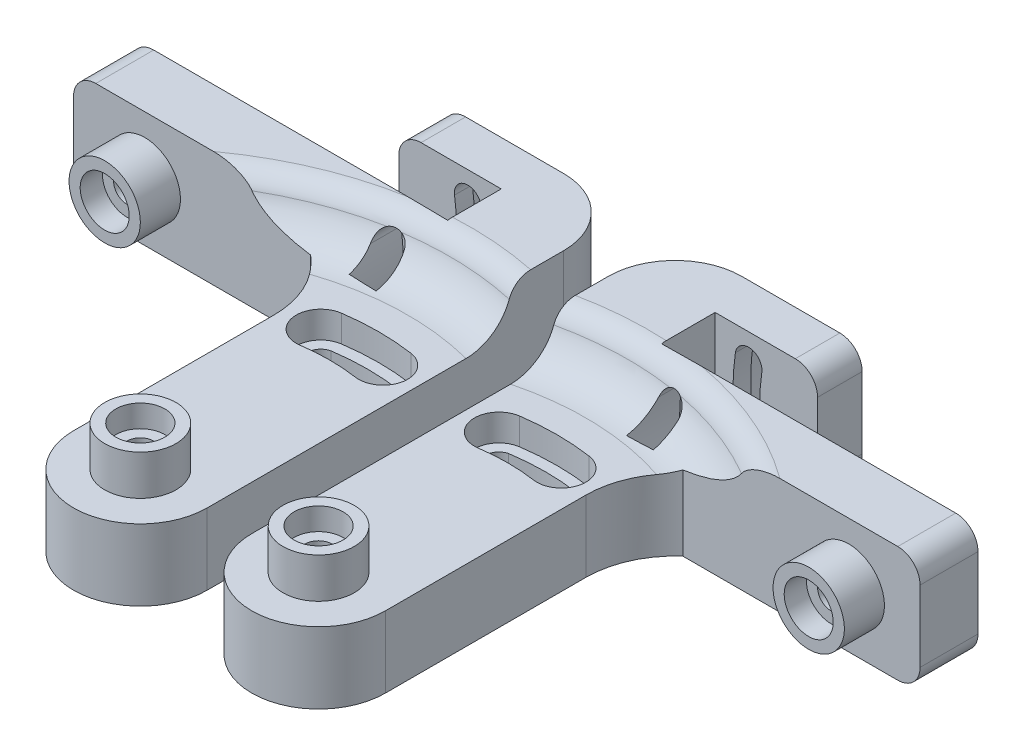
SolidWorks part; units mm, degrees
note: The reader was unsure of these and kept them because the rebuilt part matched: shared geometry of "Sketch6<8>".
ref_plane "Front Plane" through (0, 0, 0) normal (0, 0, 1) x (1, 0, 0)
ref_plane "Top Plane" through (0, 0, 0) normal (0, 1, 0) x (1, 0, 0)
ref_plane "Right Plane" through (0, 0, 0) normal (1, 0, 0) x (0, 0, -1)
sketch "Sketch1" plane through (0, 0, 0) normal (0, 1, 0) x (1, 0, 0)
  line L0 (0, 0) -> (0, 24) construction
  line L1 (0, -7.5) -> (0, 49000) construction
  line L2 (-7.5, 36.5) -> (-37.5, 36.5)
  line L3 (-37.5, 36.5) -> (-37.5, 32.5)
  line L5 (7.5, 0) -> (7.5, 40)
  line L6 (0, 47.5) -> (-13.5, 47.5)
  line L7 (-13.5, 47.5) -> (-13.5, 42.5)
  line L9 (-37.5, 32.5) -> (-17.5, 32.5)
  line L12 (-7.5, 0) -> (-7.5, 22.5)
  line L15 (-2, 42.5) -> (-2, 36.5)
  line L16 (-2, 36.5) -> (-7.5, 36.5)
  line L17 (-2, 42.5) -> (-13.5, 42.5)
  circle A1 centre (0, 0) radius 1.5
  arc A3 (3.5, 23.7434) -> (-3.5, 23.7434) centre (0, 0) ccw construction
  arc A4 (-3.8223, 25.2084) -> (-3.2806, 22.2596) centre (-3.5, 23.7434) ccw
  arc A5 (3.1485, 22.2786) -> (3.8936, 25.1975) centre (3.5, 23.7434) ccw
  arc A7 (3.8936, 25.1975) -> (-3.8223, 25.2084) centre (0, 0) ccw
  arc A8 (3.1485, 22.2786) -> (-3.2806, 22.2596) centre (0, 0) ccw
  arc A9 (7.5, 40) -> (0, 47.5) centre (0, 40) ccw
  arc A16 (-7.5, 0) -> (7.5, 0) centre (0, 0) ccw
  arc A17 (-7.5, 22.5) -> (-17.5, 32.5) centre (-17.5, 22.5) ccw
  dimension "D3" = 3
  dimension "D6" = 3
  dimension "D7" = 40
  dimension "D8" = 15
  dimension "D11" = 10
  dimension "D12" = 2
  dimension "D2" = 24
  dimension "D4" = 3.5
  dimension "D5" = 3.5
  dimension "D9" = 5
  dimension "D13" = 13.5
  dimension "D14" = 45
  dimension "D15" = 4
extrude "Boss-Extrude1" add sketch "Sketch1" along normal blind 8
sketch "Sketch2" plane through (0, 8, 0) normal (0, 1, 0) x (1, 0, 0)
  circle A0 centre (0, 0) radius 4
  circle A2 centre (0, 0) radius 1.5
  dimension "D1" = 8
  dimension "D2" = 3
extrude "Boss-Extrude2" add sketch "Sketch2" along normal blind 2
sketch "Sketch4" plane through (0, 10, 0) normal (0, 1, 0) x (1, 0, 0)
  circle A0 centre (0, 0) radius 4
  circle A1 centre (0, 0) radius 2.75
  dimension "D1" = 5.5
  dimension "D2" = 8
extrude "Boss-Extrude3" add sketch "Sketch4" along normal blind 2.5
sketch "Sketch5" plane through (0, 8, 0) normal (0, 1, 0) x (1, 0, 0)
  arc A0 (-3.901, 26.464) -> (-3.099, 21.0228) centre (-3.5, 23.7434) ccw
  arc A1 (3.099, 21.0228) -> (3.901, 26.464) centre (3.5, 23.7434) ccw
  arc A2 (3.901, 26.464) -> (-3.901, 26.464) centre (0, 0) ccw
  arc A3 (3.099, 21.0228) -> (-3.099, 21.0228) centre (0, 0) ccw
  dimension "D1" = 5.5
  dimension "D2" = 5.5
extrude "Cut-Extrude1" cut sketch "Sketch5" against normal blind 3
sketch "Sketch11" plane through (0, 8, 0) normal (0, 1, 0) x (1, 0, 0)
  line L0 (-2, 42.5) -> (-13.5, 42.5)
  line L3 (0, 47.5) -> (-13.5, 47.5)
  line L4 (-13.5, 47.5) -> (-13.5, 42.5)
  line L14 (-13.5, 42.5) -> (-2, 42.5)
  line L16 (-2, 36.5) -> (-37.5, 36.5)
  line L17 (-37.5, 36.5) -> (-37.5, 32.5)
  line L18 (-37.5, 32.5) -> (-17.5, 32.5)
  line L19 (-7.5, 22.5) -> (-7.5, 0)
  line L20 (7.5, 0) -> (7.5, 40)
  line L21 (0, 47.5) -> (-13.5, 47.5)
  line L27 (-2, 36.5) -> (-37.5, 36.5)
  line L28 (-37.5, 36.5) -> (-37.5, 32.5)
  line L29 (-37.5, 32.5) -> (-17.5, 32.5)
  line L30 (-7.5, 22.5) -> (-7.5, 0)
  line L31 (7.5, 0) -> (7.5, 40)
  line L34 (-13.5, 47.5) -> (-13.5, 42.5)
  line L37 (-2, 42.5) -> (-2, 36.5)
  line L38 (-2, 42.5) -> (-2, 36.5)
  arc A0 (7.5, 34.187) -> (-14.2635, 31.9618) centre (0, 0) ccw
  arc A3 (-7.5, 22.5) -> (-17.5, 32.5) centre (-17.5, 22.5) ccw
  arc A4 (-7.5, 0) -> (7.5, 0) centre (0, 0) ccw
  arc A5 (7.5, 40) -> (0, 47.5) centre (0, 40) ccw
  arc A6 (-7.5, 22.5) -> (-17.5, 32.5) centre (-17.5, 22.5) ccw
  arc A7 (-7.5, 0) -> (7.5, 0) centre (0, 0) ccw
  arc A8 (7.5, 40) -> (0, 47.5) centre (0, 40) ccw
  dimension "D2" = 35
  dimension "D1" = 0
extrude "Boss-Extrude4" add sketch "Sketch11" along normal blind 5
sketch "Sketch12" plane through (0, 0, -32.5) normal (0, 0, 1) x (1, 0, 0)
  line L8 (-37.5, 0) -> (-17.5, 0)
  line L9 (-17.5, 0) -> (-17.5, 13)
  line L10 (-17.5, 13) -> (-37.5, 13)
  line L11 (-37.5, 13) -> (-37.5, 0)
  line L12 (-37.5, 0) -> (-17.5, 0)
  line L13 (-17.5, 0) -> (-17.5, 13)
  line L14 (-17.5, 13) -> (-37.5, 13)
  line L15 (-37.5, 13) -> (-37.5, 0)
  dimension "D1" = 0
extrude "Boss-Extrude5" add sketch "Sketch12" along normal blind 2.5
sketch "Sketch14" plane through (0, 0, 0) normal (0, 1, 0) x (1, 0, 0)
  line L0 (-17.5, 30.3109) -> (-17.5, 32.5)
  arc A0 (-14.2635, 31.9618) -> (-17.5, 30.3109) centre (0, 0) ccw
  arc A1 (-14.2635, 31.9618) -> (-17.5, 32.5) centre (-17.5, 22.5) ccw construction
  arc A2 (-14.2635, 31.9618) -> (-17.5, 32.5) centre (-17.5, 22.5) ccw
extrude "Boss-Extrude6" add sketch "Sketch14" along normal up to surface (13 mm away) up to face at (-11.5722, 13, -37.9233)
sketch "Sketch15" plane through (0, 0, 0) normal (0, 1, 0) x (1, 0, 0)
  line L0 (-17.5, 30) -> (-17.5, 30.3109) construction
  line L1 (-17.5, 30) -> (-17.5, 30.3109)
  line L2 (-17.5, 30) -> (-10.8856, 30)
  arc A0 (-7.5, 22.5) -> (-14.2635, 31.9618) centre (-17.5, 22.5) ccw construction
  arc A1 (-10.8856, 30) -> (-14.2635, 31.9618) centre (-17.5, 22.5) ccw
  arc A2 (7.5, 34.187) -> (-17.5, 30.3109) centre (0, 0) ccw construction
  arc A3 (-14.2635, 31.9618) -> (-17.5, 30.3109) centre (0, 0) ccw
extrude "Boss-Extrude7" add sketch "Sketch15" along normal up to surface (8 mm away) up to face at (-2.585, 8, -16.7954)
sketch "Sketch16" plane through (0, 13, 0) normal (0, 1, 0) x (1, 0, 0)
  circle A0 centre (0, 0) radius 35
  circle A1 centre (0, 0) radius 33.5019
extrude "Cut-Extrude4" cut sketch "Sketch16" against normal up to surface (5 mm away) up to face at (-6.4916, 8, -20.3143)
fillet "Fillet2" radius 5 1 edges at (-5.6649, 8, -34.5385)
sketch "Sketch6" plane through (0, 0, -47.5) normal (0, 0, -1) x (-1, 0, 0)
  line L0 (2, 0) -> (37.5, 0) construction
  line L1 (37.5, 13) -> (37.5, 0) construction
  line L2 (29.5, 6.5) -> (-18.8, 6.5) construction
  line L3 (29.5, -993.5) -> (29.5, 49006.5) construction
  circle A0 centre (29.5, 6.5) radius 1.5
  circle A1 centre (5.5, 6.5) radius 1.5 construction
  arc A3 (7.2405, 9.7812) -> (4.2726, 10.2188) centre (5.7566, 10) ccw
  arc A4 (4.2726, 2.7812) -> (7.2405, 3.2187) centre (5.7566, 3) ccw
  arc A8 (7.2405, 9.7812) -> (7.2405, 3.2187) centre (29.5, 6.5) ccw
  arc A9 (4.2726, 10.2188) -> (4.2726, 2.7812) centre (29.5, 6.5) ccw
  arc A14 (8.4772, 9.599) -> (3.036, 10.401) centre (5.7566, 10) ccw
  arc A18 (3.036, 10.401) -> (3.036, 2.599) centre (29.5, 6.5) ccw
  arc A19 (8.4772, 9.599) -> (8.4772, 3.401) centre (29.5, 6.5) ccw
  arc A20 (3.036, 2.599) -> (8.4772, 3.401) centre (5.7566, 3) ccw
  dimension "D1" = 3
  dimension "D4" = 3
  dimension "D8" = 3
  dimension "D9" = 3
  dimension "D10" = 25.5
  dimension "D11" = 5.5
  dimension "D12" = 22.5
  dimension "D13" = 2.75
  dimension "D2" = 6.5
  dimension "D3" = 24
  dimension "D5" = 8
  dimension "D6" = 3.5
  dimension "D7" = 3.5
extrude "Cut-Extrude5" cut sketch "Sketch6" against normal blind 17 contours A3 A9 A4 A8 | A0
extrude "Cut-Extrude6" cut sketch "Sketch6<8>" against normal blind 3
sketch "Sketch6<8>" plane through (0, 0, -47.5) normal (0, 0, -1) x (-1, 0, 0) same geometry as "Sketch6"
sketch "Sketch17" plane through (0, 0, -30) normal (0, 0, 1) x (1, 0, 0)
  circle A0 centre (-29.5, 6.5) radius 4
  circle A1 centre (-29.5, 6.5) radius 1.5
  dimension "D1" = 8
  dimension "D2" = 3
extrude "Boss-Extrude8" add sketch "Sketch17" along normal blind 2
sketch "Sketch18" plane through (0, 0, -28) normal (0, 0, 1) x (1, 0, 0)
  circle A0 centre (-29.5, 6.5) radius 4
  circle A1 centre (-29.5, 6.5) radius 2.75
  dimension "D1" = 5.5
  dimension "D2" = 8
extrude "Boss-Extrude9" add sketch "Sketch18" along normal blind 2.5
fillet "Fillet3" radius 2.5 5 edges at (-13.5, 0, -45) (-13.5, 13, -45) (-37.5, 0, -33.25) (-37.5, 13, -33.25) (-5.6649, 13, -34.5385)
ref_plane "Plane1" through (10, 0, 0) normal (1, 0, 0) x (0, 0, -1)
sketch "Sketch21" plane through (0, 0, -30) normal (0, 0, 1) x (1, 0, 0)
  circle A1 centre (-29.5, 6.5) radius 1.5
  circle A2 centre (-29.5, 6.5) radius 1.5
  dimension "D1" = 0
extrude "Cut-Extrude7" cut sketch "Sketch21" against normal blind 10
mirror "Mirror4" about plane through (10, 0, 0) normal (1, 0, 0) of bodies 124
